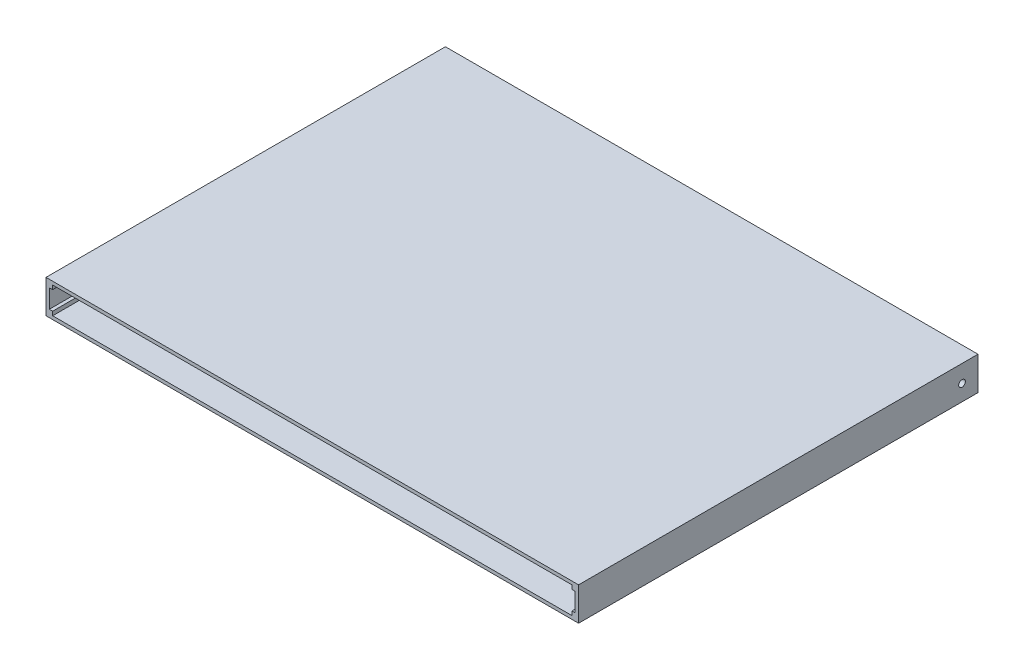
SolidWorks part; units mm, degrees
ref_plane "Front Plane" through (0, 0, 0) normal (0, 0, 1) x (1, 0, 0)
ref_plane "Top Plane" through (0, 0, 0) normal (0, 1, 0) x (1, 0, 0)
ref_plane "Right Plane" through (0, 0, 0) normal (1, 0, 0) x (0, 0, -1)
sketch "Sketch1" plane through (0, 0, 0) normal (0, 1, 0) x (1, 0, 0)
  line L1 (-254, 190.5) -> (254, 190.5)
  line L2 (-254, 190.5) -> (-254, -190.5)
  line L3 (-254, -190.5) -> (254, -190.5)
  line L4 (254, 190.5) -> (254, -190.5)
  line L5 (-254, 190.5) -> (254, -190.5) construction
  line L6 (-254, -190.5) -> (254, 190.5) construction
  point P0 (0, 0)
  dimension "D1" = 381
  dimension "D2" = 508
extrude "Boss-Extrude1" add sketch "Sketch1" along normal blind 31.75
sketch "Sketch2" plane through (0, 0, 190.5) normal (0, 0, 1) x (1, 0, 0)
  line L0 (-254, 31.75) -> (-254, 0) construction
  line L1 (250.825, 28.575) -> (-250.825, 28.575)
  line L2 (250.825, 28.575) -> (250.825, 3.175)
  line L3 (250.825, 3.175) -> (-250.825, 3.175)
  line L4 (-250.825, 28.575) -> (-250.825, 3.175)
  line L5 (250.825, 28.575) -> (-250.825, 3.175) construction
  line L6 (250.825, 3.175) -> (-250.825, 28.575) construction
  line L7 (254, 31.75) -> (254, 0) construction
  line L8 (-254, 31.75) -> (254, 31.75) construction
  line L9 (-254, 0) -> (254, 0) construction
  point P0 (0, 15.875)
  dimension "D1" = 3.175
  dimension "D2" = 3.175
  dimension "D3" = 3.175
  dimension "D4" = 3.175
extrude "Cut-Extrude1" cut sketch "Sketch2" against normal blind 342.9
sketch "Sketch3" plane through (0, 0, 190.5) normal (0, 0, 1) x (1, 0, 0)
  line L0 (0, -55) -> (0, 55) construction
  line L1 (-250.825, 28.575) -> (-247.65, 28.575)
  line L2 (-250.825, 28.575) -> (-250.825, 24.765)
  line L3 (-250.825, 24.765) -> (-247.65, 24.765)
  line L4 (-247.65, 28.575) -> (-247.65, 24.765)
  line L5 (-250.825, 3.175) -> (-247.65, 3.175)
  line L6 (-250.825, 3.175) -> (-250.825, 6.985)
  line L7 (-250.825, 6.985) -> (-247.65, 6.985)
  line L8 (-247.65, 3.175) -> (-247.65, 6.985)
  line L9 (250.825, 6.985) -> (247.65, 6.985)
  line L10 (247.65, 3.175) -> (247.65, 6.985)
  line L11 (250.825, 3.175) -> (247.65, 3.175)
  line L12 (250.825, 3.175) -> (250.825, 6.985)
  line L13 (250.825, 24.765) -> (247.65, 24.765)
  line L14 (247.65, 28.575) -> (247.65, 24.765)
  line L15 (250.825, 28.575) -> (247.65, 28.575)
  line L16 (250.825, 28.575) -> (250.825, 24.765)
  dimension "D1" = 3.175
  dimension "D2" = 3.81
extrude "Boss-Extrude2" add sketch "Sketch3" against normal blind 35.56
sketch "Sketch4" plane through (-254, 0, 0) normal (-1, 0, 0) x (0, 0, 1)
  line L2 (-190.5, 0) -> (190.5, 0) construction
  line L3 (190.5, 31.75) -> (190.5, 0) construction
  circle A0 centre (-175.26, 15.24) radius 3.175
  dimension "D1" = 6.35
  dimension "D2" = 15.24
  dimension "D3" = 365.76
extrude "Cut-Extrude2" cut sketch "Sketch4" against normal blind 25.4
extrude "Cut-Extrude3" cut sketch "Sketch4<2>" along normal blind 25.4 from surface starting at face at (254, 15.875, 0)
sketch "Sketch4<2>" plane through (-254, 0, 0) normal (-1, 0, 0) x (0, 0, 1) same geometry as "Sketch4"
